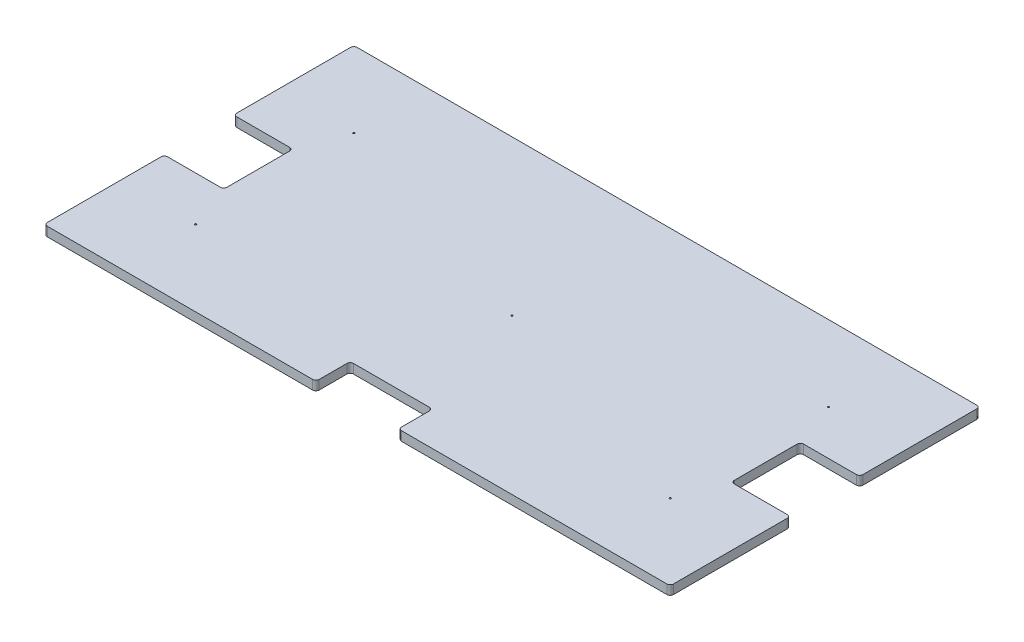
SolidWorks part; units mm, degrees
ref_plane "Front Plane" through (0, 0, 0) normal (0, 0, 1) x (1, 0, 0)
ref_plane "Top Plane" through (0, 0, 0) normal (0, 1, 0) x (1, 0, 0)
ref_plane "Right Plane" through (0, 0, 0) normal (1, 0, 0) x (0, 0, -1)
sketch "Sketch1" plane through (0, 0, 0) normal (0, 1, 0) x (1, 0, 0)
  line L1 (-603.25, -298.45) -> (603.25, -298.45)
  line L2 (-603.25, -298.45) -> (-603.25, 298.45)
  line L3 (-603.25, 298.45) -> (603.25, 298.45)
  line L4 (603.25, -298.45) -> (603.25, 298.45)
  line L5 (-603.25, -298.45) -> (603.25, 298.45) construction
  line L6 (-603.25, 298.45) -> (603.25, -298.45) construction
  point P0 (0, 0)
  dimension "D1" = 1206.5
  dimension "D2" = 596.9
extrude "Boss-Extrude1" add sketch "Sketch1" along normal blind 17.78
hole_wizard "1/8 (0.125) Diameter Hole1" positions "Sketch2" profile "Sketch3" hole size "1/8" standard "ANSI Inch" end condition through all
sketch "Sketch2" plane through (0, 17.78, 0) normal (0, 1, 0) x (1, 0, 0)
  line L1 (-457.2, -152.4) -> (457.2, -152.4) construction
  line L2 (-457.2, -152.4) -> (-457.2, 152.4) construction
  line L3 (-457.2, 152.4) -> (457.2, 152.4) construction
  line L4 (457.2, -152.4) -> (457.2, 152.4) construction
  line L5 (-457.2, -152.4) -> (457.2, 152.4) construction
  line L6 (-457.2, 152.4) -> (457.2, -152.4) construction
  point P0 (0, 0)
  point P1 (457.2, 152.4)
  point P50 (-457.2, -152.4)
  point P51 (-457.2, 152.4)
  point P52 (457.2, -152.4)
  point P63 (0, 0)
  dimension "D1" = 914.4
  dimension "D2" = 304.8
sketch "Sketch3" plane through (0, 17.78, 0) normal (1, 0, 0) x (0, 0, 1)
  line L0 (0, 0) -> (0, 17.78)
  line L1 (0, 17.78) -> (1.5875, 17.78)
  line L2 (1.5875, 17.78) -> (1.5875, 0)
  line L5 (1.5875, 0) -> (0, 0)
  line L11 (0, -6.35) -> (0, 107.95) construction
  dimension "Thru Hole Dia." = 3.175
  dimension "Thru Hole Depth" = 17.78
fillet "Fillet1" radius 6.35 4 edges at (603.25, 8.89, -298.45) (603.25, 8.89, 298.45) (-603.25, 8.89, 298.45) (-603.25, 8.89, -298.45)
sketch "Sketch4" plane through (0, 17.78, 0) normal (0, 1, 0) x (1, 0, 0)
  line L0 (0, 298.45) -> (0, -298.45) construction
  line L1 (596.9, 298.45) -> (-596.9, 298.45) construction
  line L2 (-596.9, -298.45) -> (596.9, -298.45) construction
  line L3 (-603.25, 0) -> (603.25, 0) construction
  line L4 (-79.375, -232.41) -> (79.375, -232.41)
  line L5 (-79.375, -232.41) -> (-79.375, -298.45)
  line L6 (-79.375, -298.45) -> (79.375, -298.45)
  line L7 (79.375, -232.41) -> (79.375, -298.45)
  line L8 (-79.375, -232.41) -> (79.375, -298.45) construction
  line L9 (-79.375, -298.45) -> (79.375, -232.41) construction
  line L10 (-603.25, 292.1) -> (-603.25, -292.1) construction
  line L11 (603.25, -292.1) -> (603.25, 292.1) construction
  line L13 (-488.95, 66.675) -> (-603.25, 66.675)
  line L14 (-488.95, 66.675) -> (-488.95, -66.675)
  line L15 (-488.95, -66.675) -> (-603.25, -66.675)
  line L16 (-603.25, 66.675) -> (-603.25, -66.675)
  line L17 (-488.95, 66.675) -> (-603.25, -66.675) construction
  line L18 (-488.95, -66.675) -> (-603.25, 66.675) construction
  line L19 (488.95, 66.675) -> (603.25, 66.675)
  line L20 (488.95, 66.675) -> (488.95, -66.675)
  line L21 (488.95, -66.675) -> (603.25, -66.675)
  line L22 (603.25, 66.675) -> (603.25, -66.675)
  line L23 (488.95, 66.675) -> (603.25, -66.675) construction
  line L24 (488.95, -66.675) -> (603.25, 66.675) construction
  point P6 (0, -265.43)
  point P17 (-546.1, 0)
  point P22 (546.1, 0)
  dimension "D1" = 158.75
  dimension "D2" = 66.04
  dimension "D3" = 133.35
  dimension "D4" = 114.3
extrude "Cut-Extrude1" cut sketch "Sketch4" against normal through all
fillet "Fillet2" radius 6.35 12 edges at (79.375, 8.89, 298.45) (-79.375, 8.89, 298.45) (-79.375, 8.89, 232.41) (79.375, 8.89, 232.41) (-603.25, 8.89, 66.675) (-603.25, 8.89, -66.675) (-488.95, 8.89, 66.675) (-488.95, 8.89, -66.675) (603.25, 8.89, 66.675) (488.95, 8.89, 66.675) (488.95, 8.89, -66.675) (603.25, 8.89, -66.675)
